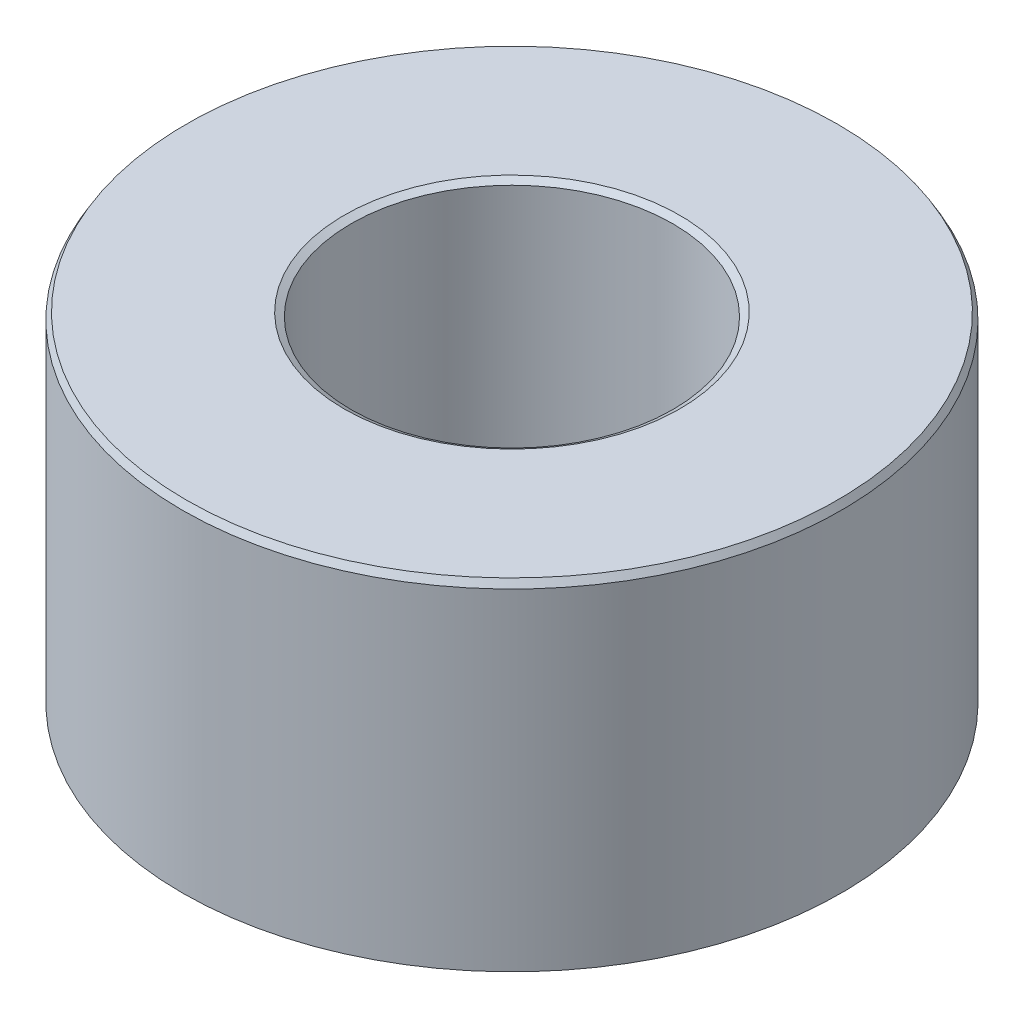
SolidWorks part; units mm, degrees
ref_plane "Front Plane" through (0, 0, 0) normal (0, 0, 1) x (1, 0, 0)
ref_plane "Top Plane" through (0, 0, 0) normal (0, 1, 0) x (1, 0, 0)
ref_plane "Right Plane" through (0, 0, 0) normal (1, 0, 0) x (0, 0, -1)
sketch "Sketch1" plane through (0, 0, 0) normal (0, 1, 0) x (1, 0, 0)
  circle A0 centre (0, 0) radius 45
  dimension "SLEEVE_OD" = 90
extrude "Boss-Extrude1" add sketch "Sketch1" along normal blind 46.735
sketch "Sketch2" plane through (0, 0, 0) normal (0, 1, 0) x (1, 0, 0)
  circle A0 centre (0, 0) radius 21.9787
  dimension "BORE_D" = 43.9574
extrude "Cut-Extrude1" cut sketch "Sketch2" along normal through all
chamfer "Chamfer1" distance 0.9347 angle 30 4 edges at (0, 46.735, 21.9787) (0, 0, 21.9787) (0, 0, 45) (0, 46.735, 45) first distance on face at (0, 46.735, 21.9787) first distance on face at (0, 0, 21.9787) first distance on face at (0, 46.735, 45)
